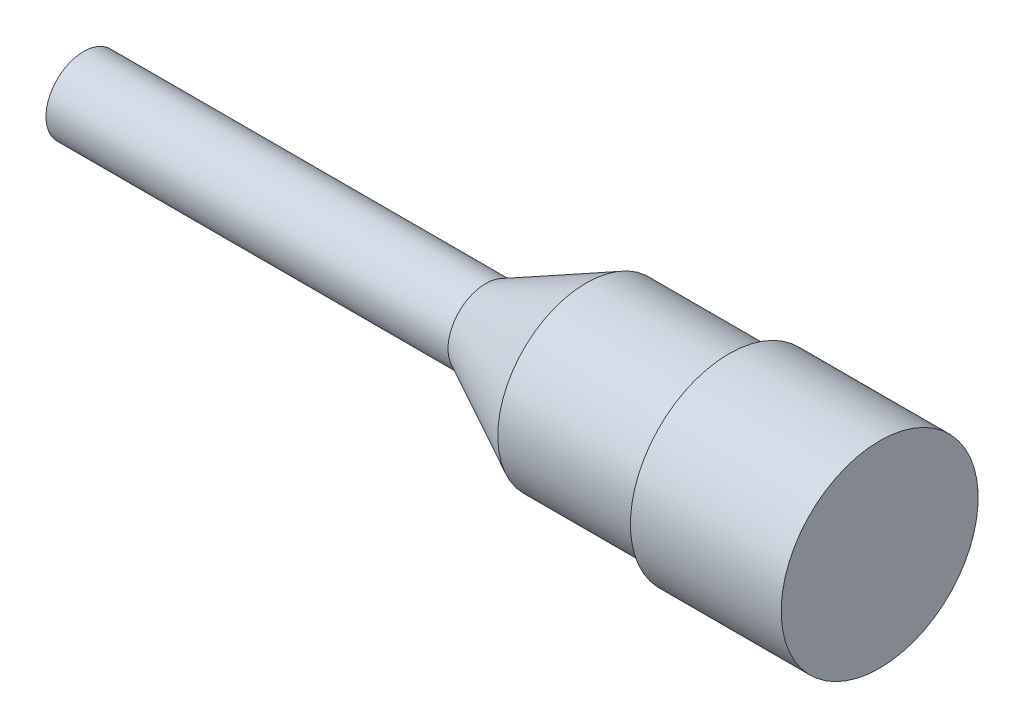
SolidWorks part; units mm, degrees
ref_plane "XY" through (0, 0, 0) normal (0, 0, 1) x (1, 0, 0)
ref_plane "XZ" through (0, 0, 0) normal (0, 1, 0) x (1, 0, 0)
ref_plane "YZ" through (0, 0, 0) normal (1, 0, 0) x (0, 0, -1)
ref_axis "X" through (-88.99, 0, 0) along (1, 0, 0)
ref_axis "Y" through (0, -55, 0) along (0, 1, 0)
ref_axis "Z" through (0, 0, 55) along (0, 0, -1)
sketch "Sketch1" plane through (0, 0, 0) normal (0, 0, 1) x (1, 0, 0)
  line L0 (0, 0) -> (-100.584, 0)
  line L2 (-49.784, 4.7625) -> (-37.084, 11.176)
  line L4 (-19.05, 12.446) -> (0, 12.446)
  line L5 (0, 12.446) -> (0, 0)
  line L6 (-100.584, 0) -> (-100.584, 4.7625)
  line L7 (-100.584, 4.7625) -> (-49.784, 4.7625)
  line L8 (-37.084, 11.176) -> (-19.05, 11.176)
  line L9 (-19.05, 11.176) -> (-19.05, 12.446)
  dimension "D1" = 12.446
  dimension "D2" = 19.05
  dimension "D3" = 12.7
  dimension "D4" = 4.7625
  dimension "D5" = 11.176
  dimension "D6" = 50.8
  dimension "D7" = 18.034
revolve "Revolve1" add sketch "Sketch1" angle 360 about L0
